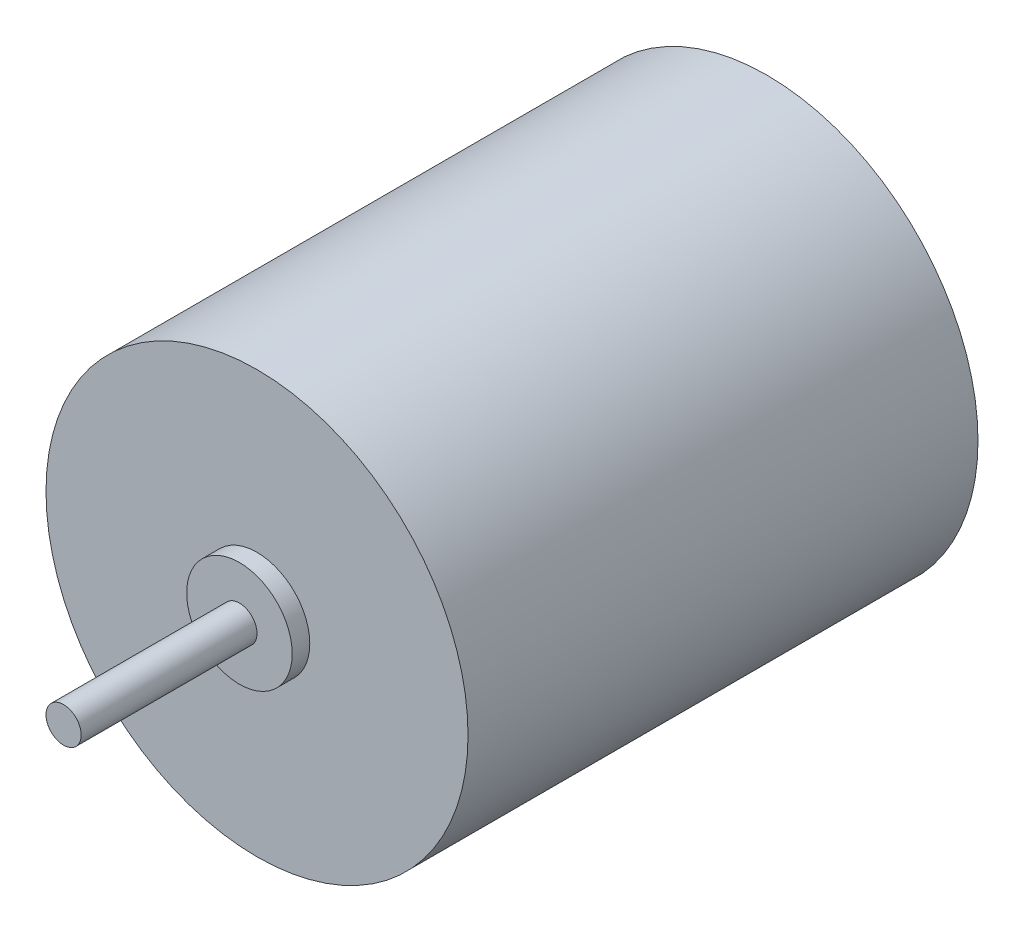
SolidWorks part; units mm, degrees
ref_plane "Front Plane" through (0, 0, 0) normal (0, 0, 1) x (1, 0, 0)
ref_plane "Top Plane" through (0, 0, 0) normal (0, 1, 0) x (1, 0, 0)
ref_plane "Right Plane" through (0, 0, 0) normal (1, 0, 0) x (0, 0, -1)
sketch "Sketch1" plane through (0, 0, 0) normal (0, 0, 1) x (1, 0, 0)
  circle A0 centre (0, 0) radius 12
  dimension "D1" = 24
extrude "Boss-Extrude1" add sketch "Sketch1" along normal blind 29
sketch "Sketch2" plane through (0, 0, 29) normal (0, 0, 1) x (1, 0, 0)
  circle A0 centre (0, 0) radius 3
  dimension "D1" = 6
extrude "Boss-Extrude2" add sketch "Sketch2" along normal blind 1
sketch "Sketch3" plane through (0, 0, 30) normal (0, 0, 1) x (1, 0, 0)
  circle A0 centre (0, 0) radius 1
  dimension "D1" = 2
extrude "Boss-Extrude3" add sketch "Sketch3" along normal blind 10 contours A0
ref_plane "Plane1" through (0, 0, -32.8) normal (0, 0, -1) x (-1, 0, 0)
sketch "Sketch4" plane through (0, 0, -32.8) normal (0, 0, -1) x (-1, 0, 0)
  circle A0 centre (0.0853, -0.3291) radius 0.5
  circle A1 centre (0, 0) radius 12 construction
  dimension "D2" = 1
  dimension "D1" = 0.34
